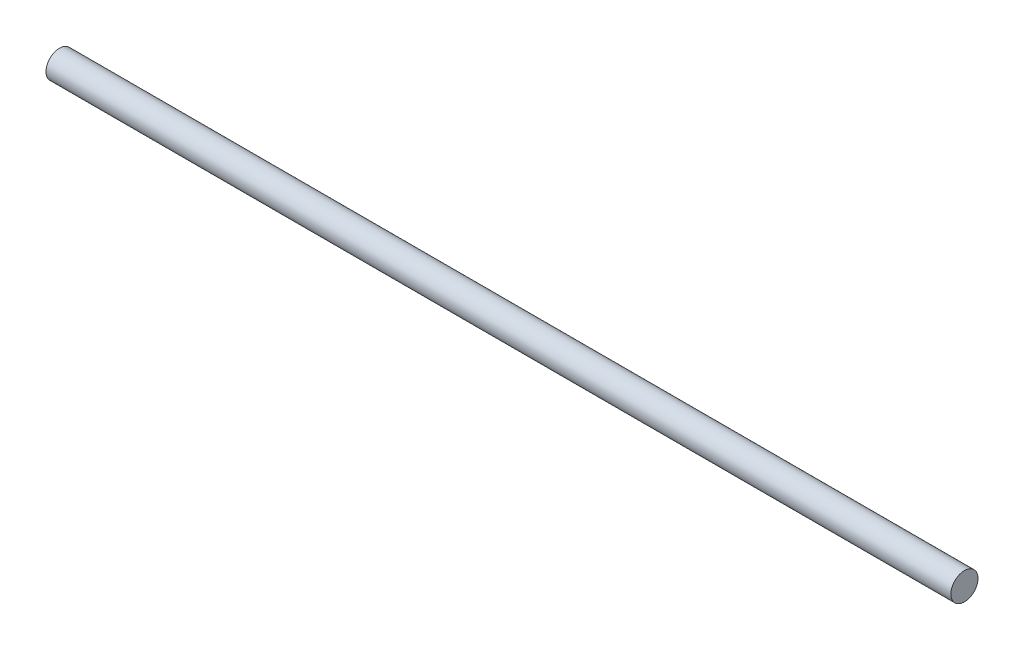
SolidWorks part; units mm, degrees
ref_plane "Front Plane" through (0, 0, 0) normal (0, 0, 1) x (1, 0, 0)
ref_plane "Top Plane" through (0, 0, 0) normal (0, 1, 0) x (1, 0, 0)
ref_plane "Right Plane" through (0, 0, 0) normal (1, 0, 0) x (0, 0, -1)
sketch "Sketch1" plane through (0, 0, 0) normal (1, 0, 0) x (0, 0, -1)
  circle A0 centre (0, 0) radius 6
  dimension "D1" = 12
extrude "Boss-Extrude1" add sketch "Sketch1" along normal blind 400
